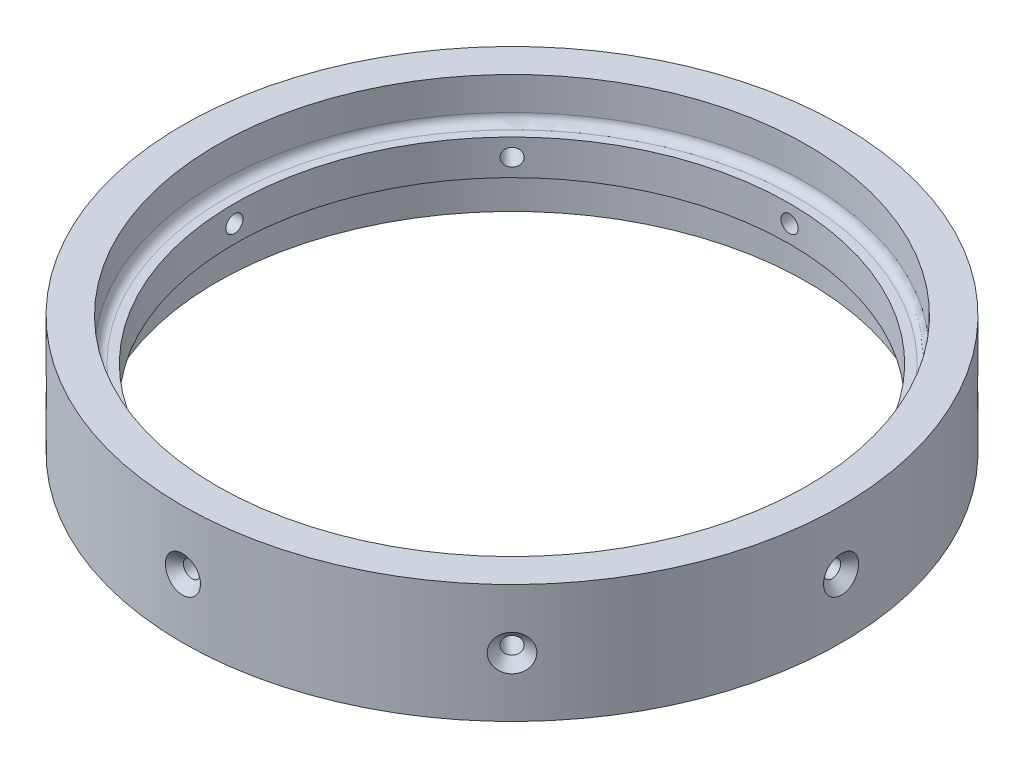
SolidWorks part; units mm, degrees
material "ABS"
ref_plane "Front Plane" through (0, 0, 0) normal (0, 0, 1) x (1, 0, 0)
ref_plane "Top Plane" through (0, 0, 0) normal (0, 1, 0) x (1, 0, 0)
ref_plane "Right Plane" through (0, 0, 0) normal (1, 0, 0) x (0, 0, -1)
sketch "Sketch1" plane through (0, 0, 0) normal (0, 1, 0) x (1, 0, 0)
  circle A0 centre (0, 0) radius 67.2
  circle A1 centre (0, 0) radius 75
  dimension "D1" = 134.4
  dimension "D2" = 150
extrude "Boss-Extrude1" add sketch "Sketch1" along normal blind 27
hole_wizard "CSK for M3.5 Flat Head Machine Screw1" positions "3DSketch1" profile "Sketch2" countersink size "M3.5" standard "ANSI Metric" end condition through all
sketch3d "3DSketch1"
  line L0 (0, 0, 0) -> (-75, 0, 0)
  line L4 (-75, 0, 0) -> (-75, 27, 0)
  circle A0 centre (0, 0, 0) radius 75 construction
  circle A1 centre (0, 27, 0) radius 75 construction
  point P0 (-75, 13.5, 0)
  point P7 (0, 75, 0)
  point P18 (0, 102, 0)
  point P19 (-75, 13.5, 0)
sketch "Sketch2" plane through (-75, 13.5, 0) normal (0, 1, 0) x (0, 0, 1)
  line L0 (0, 0) -> (0, 181.066)
  line L1 (0, 181.066) -> (1.95, 181.066)
  line L2 (1.95, 181.066) -> (1.95, 2.15)
  line L3 (1.95, 2.15) -> (4.1, 0)
  line L5 (4.1, 0) -> (0, 0)
  line L6 (-1.95, 2.15) -> (-4.1, 0) construction
  line L11 (0, -6.35) -> (0, 107.95) construction
  dimension "Thru Hole Dia." = 3.9
  dimension "Thru Hole Depth" = 181.066
  dimension "Near C'Sink Dia." = 8.2
  dimension "Near C'Sink Angle" = 90
ref_plane "Plane1" [suppressed] through (-72.85, 0, 0) normal (1, 0, 0) x (0, 0, -1)
ref_plane "Plane2" [suppressed] through (-72.85, 0, 0) normal (1, 0, 0) x (0, 0, -1)
sketch "Sketch6" plane through (0, 27, 0) normal (0, 1, 0) x (1, 0, 0)
  circle A0 centre (0, 0) radius 67.2 construction
  circle A1 centre (0, 0) radius 67.2
  circle A4 centre (0, 0) radius 57.2
  circle A5 centre (0, 0) radius 57.2
  dimension "D1" = 10
extrude "Cut-Extrude1" [suppressed] cut sketch "Sketch6" against normal through all
ref_plane "Plane3" through (0, 13.5, 0) normal (0, 1, 0) x (1, 0, 0)
sketch "Sketch7" plane through (0, 13.5, 0) normal (0, 1, 0) x (1, 0, 0)
  circle A1 centre (0, 0) radius 63.2
  circle A2 centre (0, 0) radius 67.2 construction
  circle A3 centre (0, 0) radius 67.2
  dimension "D1" = 126.4
extrude "Boss-Extrude2" add sketch "Sketch7" along normal mid plane 8
pattern_circular "CirPattern1" count 8 over 360 about axis through (0, 27, 0) along (0, -1, 0) of "CSK for M3.5 Flat Head Machine Screw1" reverse direction yes
fillet "Fillet1" radius 2 2 edges at (0, 9.5, 67.2) (0, 17.5, 67.2)
ref_plane "Plane4" through (0, 13.5, 0) normal (0, -1, 0) x (-1, 0, 0)
sketch3d "3DSketch4"
  line L0 (0, 13.5, 0) -> (-25, 13.5, 0)
  line L1 (0, 13.5, 0) -> (0, 13.5, 25)
  line L2 (0, 13.5, 0) -> (0, 27, 0)
  circle A0 centre (0, 13.5, 0) radius 25
  circle A1 centre (0, 27, 0) radius 67.2 construction
  circle A2 centre (0, 27, 0) radius 67.2
  point P2 (0, -11.5, 0)
  point P5 (0, 94.2, 0)
  point P7 (0, 94.2, 0)
  dimension "D1" = 50
ref_axis "reff wheel axis" through (0, 27, 0) along (0, -1, 0)
